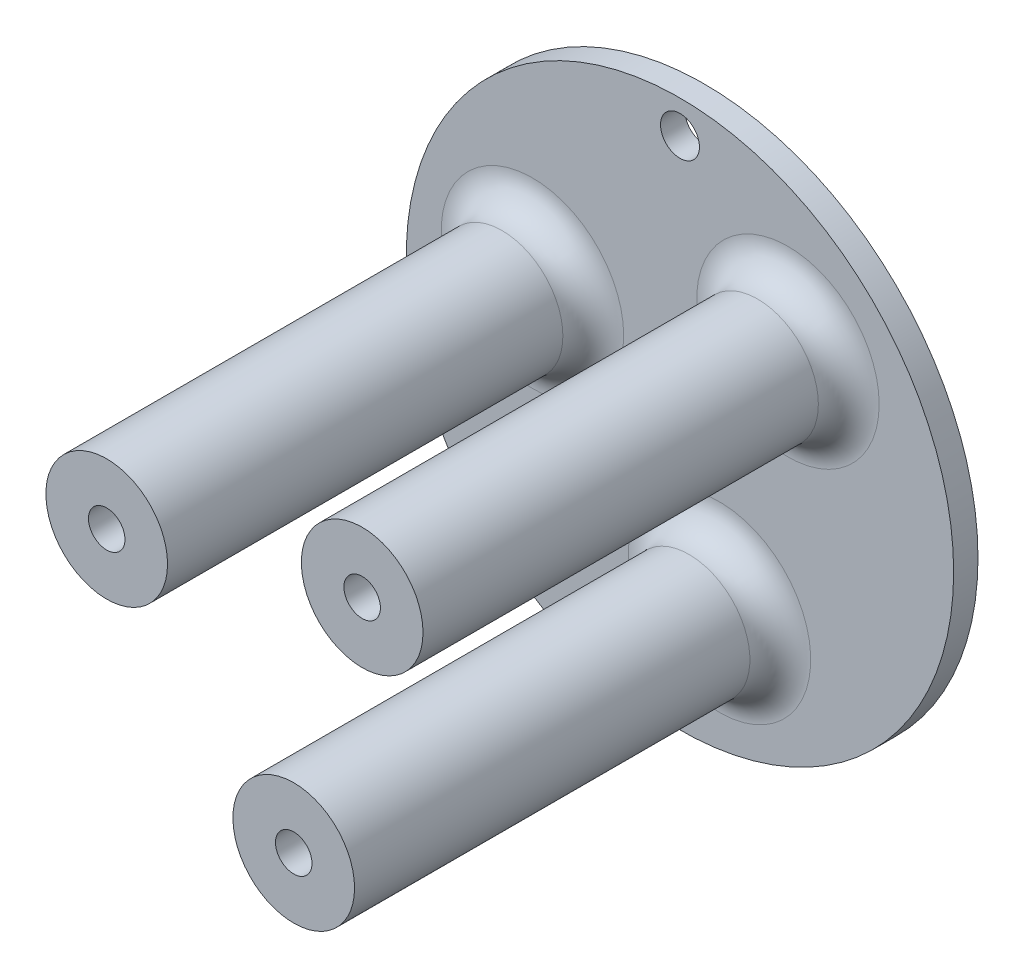
SolidWorks part; units mm, degrees
ref_plane "前视基准面" through (0, 0, 0) normal (0, 0, 1) x (1, 0, 0)
ref_plane "上视基准面" through (0, 0, 0) normal (0, 1, 0) x (1, 0, 0)
ref_plane "右视基准面" through (0, 0, 0) normal (1, 0, 0) x (0, 0, -1)
other "Configuration Table"
sketch "草图1" plane through (0, 0, 0) normal (0, 0, 1) x (1, 0, 0)
  line L0 (0, 24.4681) -> (0, -25.6239) construction
  circle A0 centre (0, 0) radius 22.5
  circle A1 centre (0, 0) radius 19.8 construction
  circle A2 centre (0, 19.8) radius 1.6
  circle A3 centre (0, -19.8) radius 1.6
  dimension "D1" = 45
  dimension "D2" = 39.6
extrude "凸台-拉伸1" add sketch "草图1" along normal blind 2
sketch "草图2" plane through (0, 0, 2) normal (0, 0, 1) x (1, 0, 0)
  line L0 (0, 0) -> (17.457, 17.457) construction
  line L1 (0, 0) -> (0, 24.653) construction
  line L2 (0, 0) -> (-12.1254, 3.249) construction
  circle A0 centre (0, 0) radius 12.5531 construction
  circle A1 centre (8.8764, 8.8764) radius 1.5
  circle A2 centre (3.249, -12.1254) radius 1.5
  circle A3 centre (-12.1254, 3.249) radius 1.5
  circle A4 centre (-12.1254, 3.249) radius 5
  circle A5 centre (8.8764, 8.8764) radius 5
  circle A6 centre (3.249, -12.1254) radius 5
  point P13 (0, 0)
  point P20 (0, 0)
  dimension "D1" = 45
  dimension "D2" = 3
  dimension "D3" = 3
  dimension "D4" = 10
  dimension "D5" = 3
extrude "凸台-拉伸2" add sketch "草图2" along normal blind 35
sketch "草图3" plane through (0, 0, 2) normal (0, 0, 1) x (1, 0, 0)
  circle A0 centre (-12.1254, 3.249) radius 1.6
  circle A1 centre (8.8764, 8.8764) radius 1.6
  circle A2 centre (3.249, -12.1254) radius 1.6
extrude "凸台-拉伸3" add sketch "草图3" along normal blind 15
fillet "圆角2" radius 2.5 3 edges at (13.8764, 8.8764, 2) (8.249, -12.1254, 2) (-7.1254, 3.249, 2)
